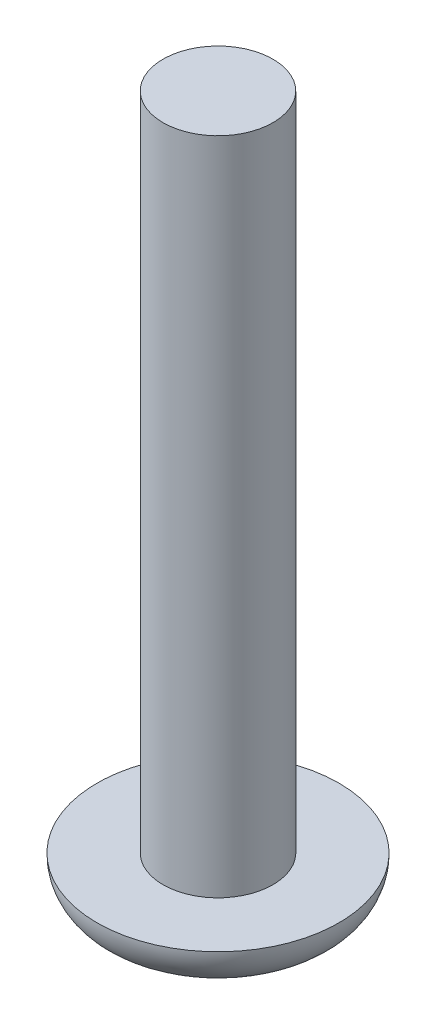
SolidWorks part; units mm, degrees
ref_plane "Front Plane" through (0, 0, 0) normal (0, 0, 1) x (1, 0, 0)
ref_plane "Top Plane" through (0, 0, 0) normal (0, 1, 0) x (1, 0, 0)
ref_plane "Right Plane" through (0, 0, 0) normal (1, 0, 0) x (0, 0, -1)
sketch "Sketch1" plane through (0, 0, 0) normal (0, 1, 0) x (1, 0, 0)
  circle A0 centre (0, 0) radius 2.5
  dimension "D1" = 5
extrude "Boss-Extrude1" add sketch "Sketch1" along normal blind 30 contours A0
sketch "Sketch2" plane through (0, 0, 0) normal (0, -1, 0) x (1, 0, 0)
  circle A0 centre (0, 0) radius 5.5
  circle A1 centre (0, 0) radius 2.5 construction
  circle A2 centre (0, 0) radius 2.5 construction
  dimension "D1" = 3
extrude "Boss-Extrude2" add sketch "Sketch2" along normal blind 2
fillet "Fillet1" radius 2 1 edges at (0, -2, -5.5)
sketch "Sketch3" plane through (0, -2, 0) normal (0, -1, 0) x (1, 0, 0)
  line L0 (0.375, 0.375) -> (1.5, 0.375)
  line L1 (-0.375, -1.5) -> (0.375, -1.5)
  line L2 (-0.375, -1.5) -> (-0.375, -0.375)
  line L3 (-0.375, 1.5) -> (0.375, 1.5)
  line L4 (0.375, -1.5) -> (0.375, -0.375)
  line L7 (-1.5, -0.375) -> (-0.375, -0.375)
  line L8 (-1.5, -0.375) -> (-1.5, 0.375)
  line L9 (-1.5, 0.375) -> (-0.375, 0.375)
  line L10 (1.5, -0.375) -> (1.5, 0.375)
  line L15 (0.375, 0.375) -> (0.375, 1.5)
  line L16 (0.375, -0.375) -> (1.5, -0.375)
  line L17 (-0.375, 0.375) -> (-0.375, 1.5)
  point P0 (0, 0)
  point P6 (0, 0)
  dimension "D1" = 3
  dimension "D2" = 0.75
extrude "Cut-Extrude1" cut sketch "Sketch3" against normal blind 1 draft 15
